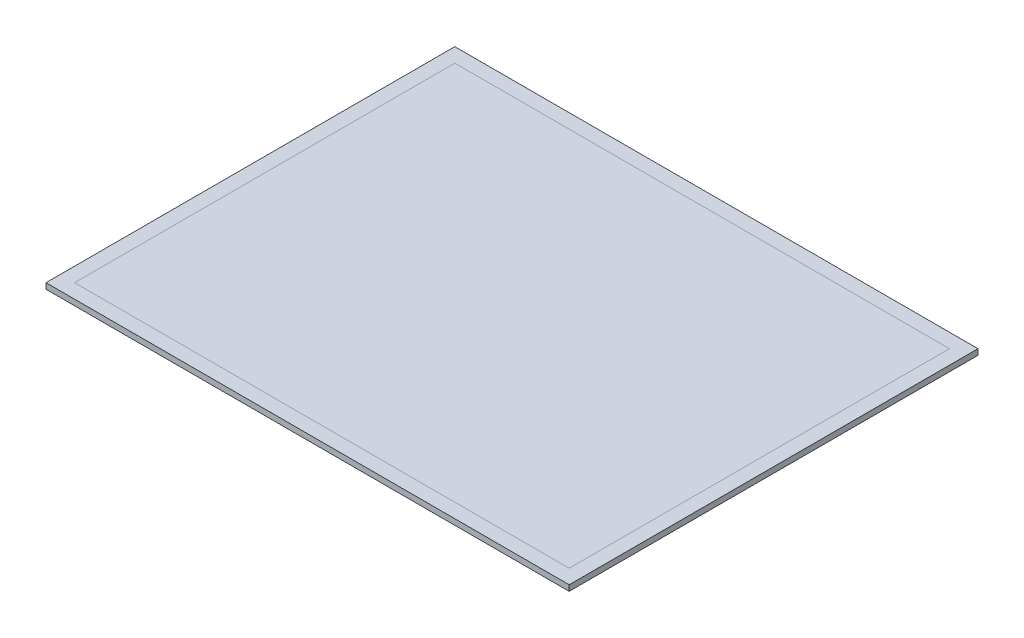
SolidWorks part; units mm, degrees
ref_plane "Front Plane" through (0, 0, 0) normal (0, 0, 1) x (1, 0, 0)
ref_plane "Top Plane" through (0, 0, 0) normal (0, 1, 0) x (1, 0, 0)
ref_plane "Right Plane" through (0, 0, 0) normal (1, 0, 0) x (0, 0, -1)
sketch "Sketch1" plane through (0, 0, 0) normal (0, 1, 0) x (1, 0, 0)
  line L0 (-86.5, -66.5) -> (-86.5, 66.5)
  line L1 (-91.5, -71.5) -> (91.5, -71.5)
  line L2 (-91.5, -71.5) -> (-91.5, 71.5)
  line L3 (-91.5, 71.5) -> (91.5, 71.5)
  line L4 (91.5, -71.5) -> (91.5, 71.5)
  line L5 (-91.5, -71.5) -> (91.5, 71.5) construction
  line L6 (-91.5, 71.5) -> (91.5, -71.5) construction
  line L7 (-86.5, 66.5) -> (86.5, 66.5)
  line L8 (86.5, -66.5) -> (86.5, 66.5)
  line L9 (-86.5, -66.5) -> (86.5, -66.5)
  point P0 (0, 0)
  dimension "D1" = 183
  dimension "D2" = 143
  dimension "D3" = 5
extrude "Boss-Extrude1" add sketch "Sketch1" along normal blind 2
extrude "Boss-Extrude2" add sketch "Sketch1<2>" along normal blind 2 separate body contours L0 L9 L8 L7 region at (0, 0, 0)
sketch "Sketch1<2>" plane through (0, 0, 0) normal (0, 1, 0) x (1, 0, 0) same geometry as "Sketch1"
